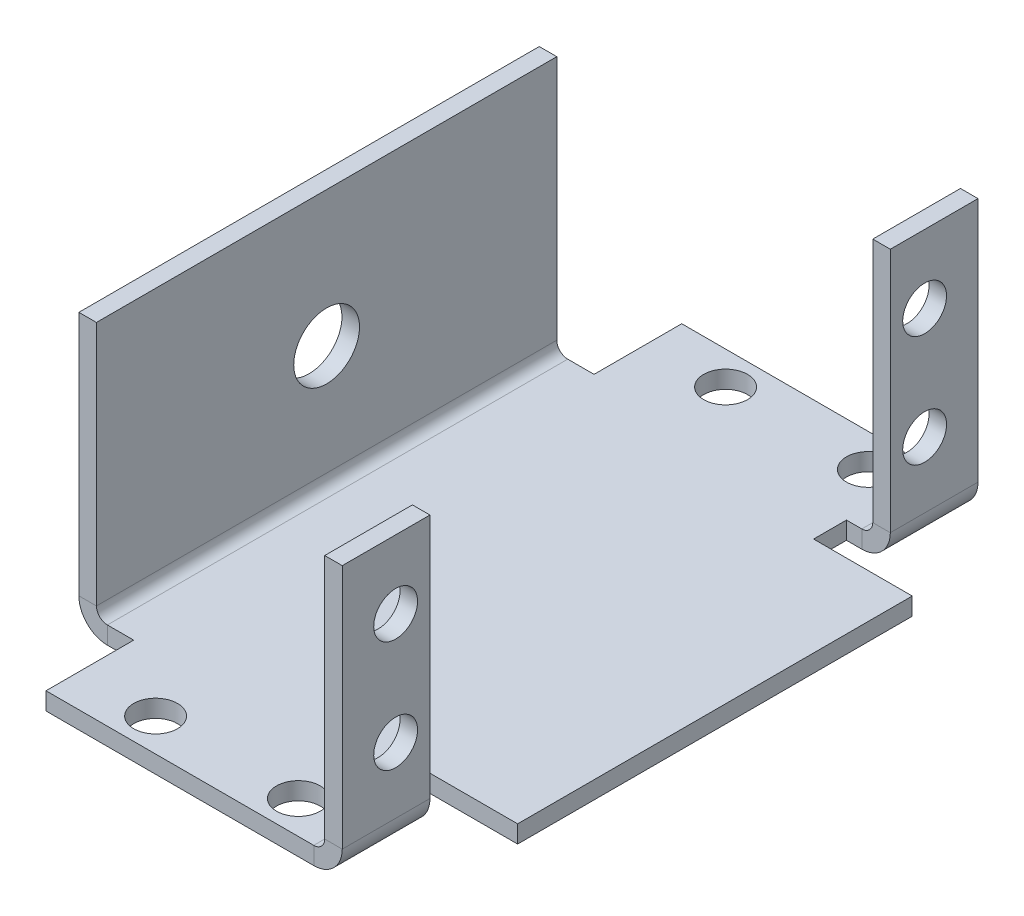
SolidWorks part; units mm, degrees
note: The reader was unsure of these and kept them because the rebuilt part matched: flange length of "Edge-Flange1".
material "1060 Alloy"
ref_plane "Front Plane" through (0, 0, 0) normal (0, 0, 1) x (1, 0, 0)
ref_plane "Top Plane" through (0, 0, 0) normal (0, 1, 0) x (1, 0, 0)
ref_plane "Right Plane" through (0, 0, 0) normal (1, 0, 0) x (0, 0, -1)
sketch "Sketch1" plane through (0, 0, 0) normal (0, 1, 0) x (1, 0, 0)
  line L0 (-18.514, 21) -> (-13.514, 21)
  line L1 (13.514, -29) -> (-13.514, -29)
  line L2 (18.514, -18) -> (18.514, 18)
  line L3 (13.514, 29) -> (-13.514, 29)
  line L4 (-18.514, -21) -> (-18.514, 21)
  line L6 (18.514, 18) -> (9.514, 18)
  line L7 (-18.514, -21) -> (-13.514, -21)
  line L8 (-13.514, 21) -> (-13.514, 29)
  line L9 (-13.514, -21) -> (-13.514, -29)
  line L10 (9.514, 18) -> (9.514, 21)
  line L11 (9.514, 21) -> (13.514, 21)
  line L12 (13.514, 21) -> (13.514, 29)
  line L13 (18.514, -18) -> (9.514, -18)
  line L14 (9.514, -18) -> (9.514, -21)
  line L15 (9.514, -21) -> (13.514, -21)
  line L16 (13.514, -21) -> (13.514, -29)
  circle A10 centre (-6.514, 26) radius 2
  circle A11 centre (6.514, 26) radius 2
  circle A12 centre (6.514, -26) radius 2
  circle A13 centre (-6.514, -26) radius 2
  point P0 (0, 0)
  point P31 (0, 0)
  dimension "D13" = 4
  dimension "D15" = 1
  dimension "D16" = 5
  dimension "D17" = 5
  dimension "D1" = 58
  dimension "D3" = 8
  dimension "D4" = 5
  dimension "D5" = 9
  dimension "D6" = 3
  dimension "D7" = 8
  dimension "D8" = 5
sheet metal parameters "Sheet-Metal1" thickness 1.6 parameters "D1"=1
base flange "Base-Flange1" sketch "Sketch1" thickness 1.6 reverse thickness direction no parameters "D1"=1
edge flange "Edge-Flange1" sketch "Sketch11" flange profiles "Sketch11", "Sketch12", "Sketch13" flange angle 90 flange length 25 flange position material inside bend radius 1 thickness 1.6 relief rectangular parameters "D6"=10, "D8"=1
sketch "Sketch11" plane through (13.514, 0, 0) normal (1, 0, 0) x (0, 0, -1)
  line L2 (-29, 0) -> (-29, 23.4)
  line L3 (-29, 23.4) -> (-21, 23.4)
  line L4 (-21, 23.4) -> (-21, 0)
  line L5 (-29, 0) -> (-21, 0) construction
  line L6 (-29, 0) -> (-21, 0)
sketch "Sketch12" plane through (13.514, 0, 0) normal (1, 0, 0) x (0, 0, -1)
  line L0 (21, 0) -> (29, 0) construction
  line L1 (21, 0) -> (29, 0)
  line L2 (21, 0) -> (21, 23.4)
  line L3 (21, 23.4) -> (29, 23.4)
  line L4 (29, 23.4) -> (29, 0)
sketch "Sketch13" plane through (-18.514, 0, 0) normal (-1, 0, 0) x (0, 0, 1)
  line L0 (-21, 0) -> (21, 0) construction
  line L1 (-21, 0) -> (21, 0)
  line L2 (-21, 0) -> (-21, 23.4)
  line L3 (-21, 23.4) -> (21, 23.4)
  line L4 (21, 23.4) -> (21, 0)
bend "EdgeBend1" bend radius 1 bend angle 90 parameters "D5"=1
bend "EdgeBend2" bend radius 1 bend angle 90 parameters "D5"=2
bend "EdgeBend3" bend radius 1 bend angle 90 parameters "D5"=3
sketch "Sketch14" plane through (-18.514, 0, 0) normal (-1, 0, 0) x (0, 0, 1)
  circle A0 centre (0, 11.0453) radius 3
  dimension "D1" = 6
extrude "Cut-Extrude1" cut sketch "Sketch14" against normal up to next normal cut yes
sketch "Sketch15" plane through (13.514, 0, 0) normal (1, 0, 0) x (0, 0, -1)
  line L0 (-21, -1.6) -> (-29, -1.6) construction
  line L3 (0, 0) -> (0, 8.2905) construction
  circle A0 centre (-24.13, 7) radius 2
  circle A1 centre (-24.13, 17.16) radius 2
  circle A2 centre (24.13, 7) radius 2
  circle A3 centre (24.13, 17.16) radius 2
  dimension "D3" = 4
  dimension "D1" = 8.6
  dimension "D2" = 10.16
  dimension "D4" = 48.26
extrude "Cut-Extrude2" cut sketch "Sketch15" against normal up to next normal cut yes
flat pattern "Flat-Pattern1" [suppressed]
sketch "Bend-Lines1" plane through (0, 0, 0) normal (0, 1, 0) x (-1, 0, 0)
sketch3d "Bounding-Box1" [suppressed]
  line L0 (-30, 0, 0) -> (-30, 58, 0) construction
  line L1 (5, 0, 0) -> (5, 58, 0) construction
  line L2 (-30, 0, 0) -> (5, 0, 0) construction
  line L3 (-30, 58, 0) -> (5, 58, 0) construction
bend of the flat pattern "Flatten-<EdgeBend1>1"
bend of the flat pattern "Flatten-<EdgeBend2>1"
bend of the flat pattern "Flatten-<EdgeBend3>1"
